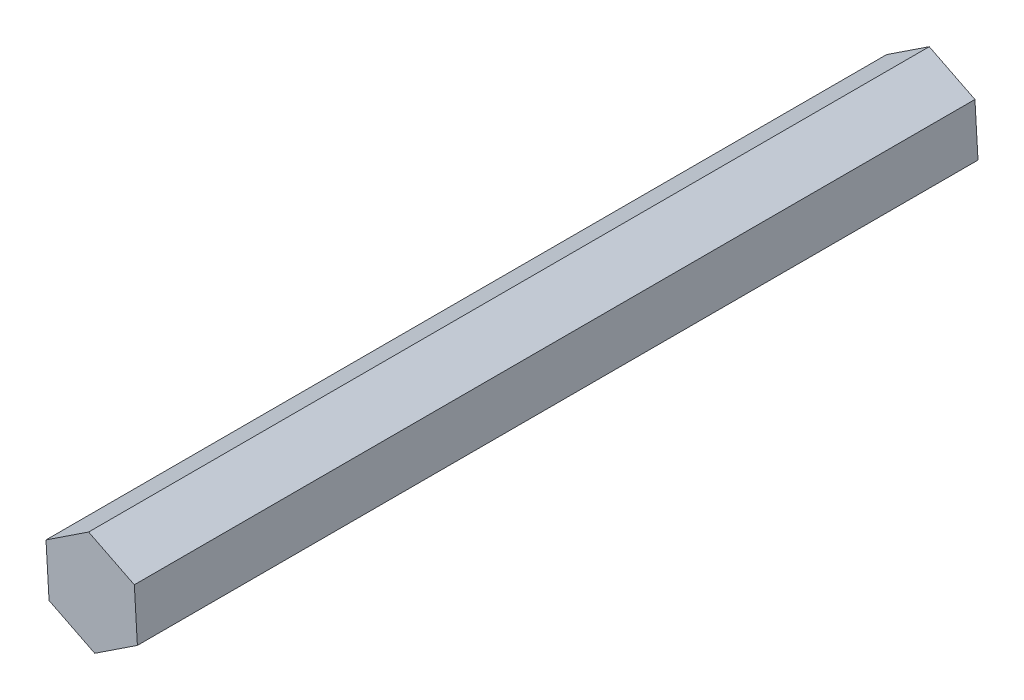
SolidWorks part; units mm, degrees
ref_plane "Front Plane" through (0, 0, 0) normal (0, 0, 1) x (1, 0, 0)
ref_plane "Top Plane" through (0, 0, 0) normal (0, 1, 0) x (1, 0, 0)
ref_plane "Right Plane" through (0, 0, 0) normal (1, 0, 0) x (0, 0, -1)
sketch "Sketch1" plane through (0, 0, 0) normal (0, 0, 1) x (1, 0, 0)
  line L1 (-6.5583, 3.2791) -> (-6.1189, -4.04)
  line L2 (-6.1189, -4.04) -> (0.4393, -7.3192)
  line L3 (0.4393, -7.3192) -> (6.5583, -3.2791)
  line L4 (6.5583, -3.2791) -> (6.1189, 4.04)
  line L5 (6.1189, 4.04) -> (-0.4393, 7.3192)
  line L6 (-0.4393, 7.3192) -> (-6.5583, 3.2791)
  circle A0 centre (0, 0) radius 6.35 construction
  dimension "D1" = 12.7
extrude "Boss-Extrude1" add sketch "Sketch1" along normal blind 120.65 contours L3 L4 L5 L6 L1 L2
